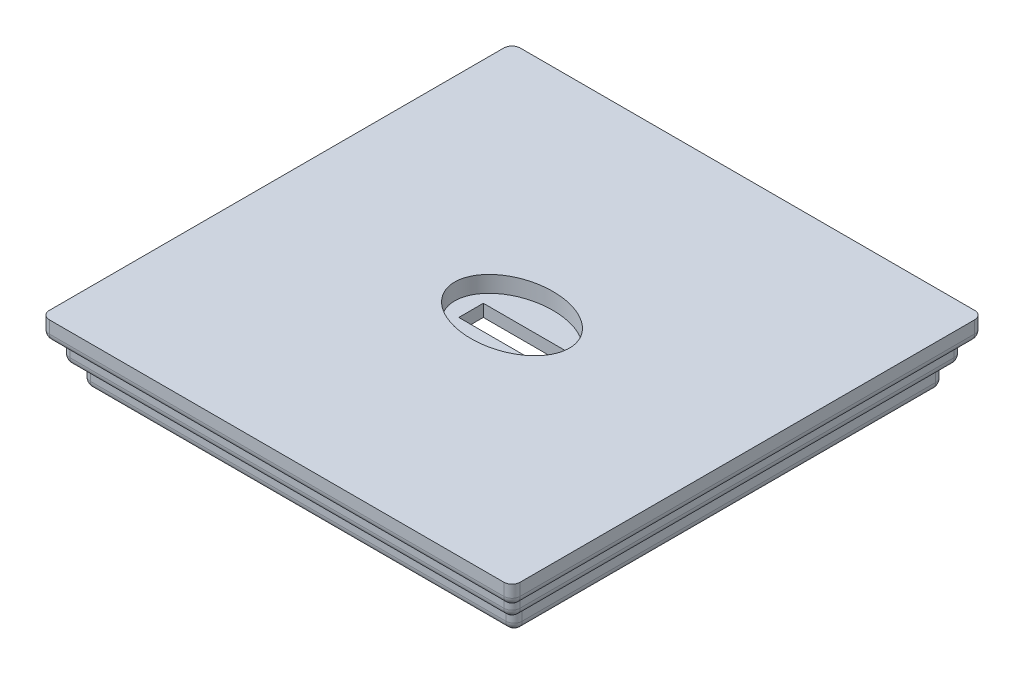
SolidWorks part; units mm, degrees
ref_plane "Front Plane" through (0, 0, 0) normal (0, 0, 1) x (1, 0, 0)
ref_plane "Top Plane" through (0, 0, 0) normal (0, 1, 0) x (1, 0, 0)
ref_plane "Right Plane" through (0, 0, 0) normal (1, 0, 0) x (0, 0, -1)
sketch "Sketch7" plane through (0, 0, 0) normal (0, 0, 1) x (1, 0, 0)
  line L0 (55, 0) -> (-55, 0) construction
  line L1 (-26.25, 2.5) -> (26.5, 2.5)
  line L2 (-26.25, 2.5) -> (-26.25, 0)
  line L3 (-26.25, 0) -> (26.5, 0)
  line L4 (26.5, 2.5) -> (26.5, 0)
  point P6 (0, 0)
  point P7 (0, 0)
  point P8 (0, 0)
  point P9 (0, 0)
  point P10 (0, 0)
  point P11 (0, 0)
extrude "Boss-Extrude4" add sketch "Sketch7" along normal blind 26.25 and the other way blind 26.25
sketch "Sketch8" plane through (0, 0, 0) normal (0, 0, 1) x (1, 0, 0)
  line L1 (-27.5, 2.5) -> (27.5, 2.5)
  line L2 (-27.5, 2.5) -> (-27.5, 5)
  line L3 (-27.5, 5) -> (27.5, 5)
  line L4 (27.5, 2.5) -> (27.5, 5)
  point P4 (0, 0)
  point P5 (0, 0)
  point P6 (0, 0)
  point P7 (0, 0)
extrude "Boss-Extrude5" add sketch "Sketch8" along normal blind 27.5 and the other way blind 27.5
sketch "Sketch9" plane through (0, 0, 0) normal (0, 0, 1) x (1, 0, 0)
  line L1 (-28.75, 7.5) -> (28.75, 7.5)
  line L2 (-28.75, 7.5) -> (-28.75, 5)
  line L3 (-28.75, 5) -> (28.75, 5)
  line L4 (28.75, 7.5) -> (28.75, 5)
  point P4 (0, 0)
  point P5 (0, 0)
  point P6 (0, 0)
  point P7 (0, 0)
extrude "Boss-Extrude6" add sketch "Sketch9" along normal blind 28.75 and the other way blind 28.75
sketch "Sketch10" plane through (0, 0, 0) normal (0, 1, 0) x (1, 0, 0)
  line L1 (-22.8, 22.8) -> (22.8, 22.8)
  line L2 (-22.8, 22.8) -> (-22.8, -22.8)
  line L3 (-22.8, -22.8) -> (22.8, -22.8)
  line L4 (22.8, 22.8) -> (22.8, -22.8)
  point P4 (-93.6274, -44.8238)
  point P5 (0, 0)
  point P6 (0, 0)
  point P7 (0, 0)
  point P8 (0, 0)
  point P9 (0, 0)
extrude "Cut-Extrude1" cut sketch "Sketch10" against normal blind 4.5 and the other way blind 4
sketch "Sketch12" plane through (0, 7.5, 0) normal (0, 1, 0) x (1, 0, 0)
  ellipse E0 centre (0, 0) end of major axis (7, 0) minor radius 5
extrude "Cut-Extrude2" cut sketch "Sketch12" against normal blind 2
sketch "Sketch13" plane through (0, 0, 0) normal (0, 1, 0) x (1, 0, 0)
  line L1 (-5, 1.5) -> (5, 1.5)
  line L2 (-5, 1.5) -> (-5, -1.5)
  line L3 (-5, -1.5) -> (5, -1.5)
  line L4 (5, 1.5) -> (5, -1.5)
extrude "Cut-Extrude3" cut sketch "Sketch13" against normal through all and the other way blind 29
fillet "Fillet4" radius 1 28 edges at (-26.25, 1.25, -26.25) (-27.5, 3.75, -27.5) (-28.75, 6.25, -28.75) (-22.8, 0, 0) (-26.25, 0, 0) (-27.5, 2.5, 0) (-28.75, 5, 0) (-28.75, 6.25, 28.75) (-27.5, 3.75, 27.5) (-26.25, 1.25, 26.25) (0, 5, -28.75) (0, 2.5, -27.5) (0.125, 0, -26.25) (26.5, 1.25, -26.25) (27.5, 3.75, -27.5) (28.75, 6.25, -28.75) (28.75, 6.25, 28.75) (0, 5, 28.75) (28.75, 5, 0) (27.5, 2.5, 0) (0, 2.5, 27.5) (27.5, 3.75, 27.5) (26.5, 1.25, 26.25) (26.5, 0, 0) (0, 0, -22.8) (22.8, 0, 0) (0, 0, 22.8) (0.125, 0, 26.25)
